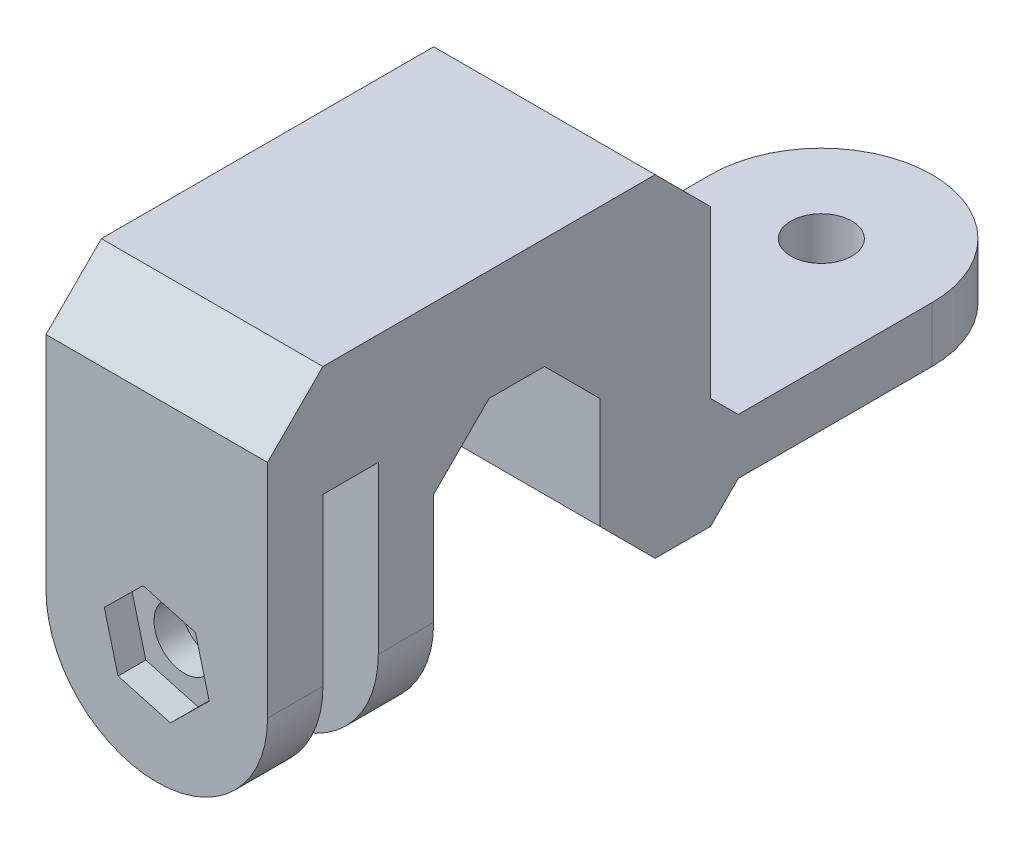
SolidWorks part; units mm, degrees
ref_plane "Front Plane" through (0, 0, 0) normal (0, 0, 1) x (1, 0, 0)
ref_plane "Top Plane" through (0, 0, 0) normal (0, 1, 0) x (1, 0, 0)
ref_plane "Right Plane" through (0, 0, 0) normal (1, 0, 0) x (0, 0, -1)
sketch "Sketch1" plane through (0, 0, 0) normal (0, 0, 1) x (1, 0, 0)
  line L0 (0, -5) -> (0, 5) construction
  line L1 (-10, -5) -> (10, -5)
  line L2 (-10, -5) -> (-10, 5)
  line L3 (-10, 5) -> (10, 5)
  line L4 (10, -5) -> (10, 5)
  dimension "D1" = 10
  dimension "D2" = 20
extrude "Boss-Extrude1" add sketch "Sketch1" along normal blind 10
sketch "Sketch3" plane through (0, 0, 0) normal (0, 0, -1) x (-1, 0, 0)
  line L0 (-10, -5) -> (-10, 5) construction
  line L1 (-10, 2.5) -> (10, 2.5)
  line L2 (-10, 2.5) -> (-10, -2.5)
  line L3 (-10, -2.5) -> (10, -2.5)
  line L4 (10, 2.5) -> (10, -2.5)
  line L5 (10, 5) -> (10, -5) construction
  line L6 (-10, 0) -> (10, 0) construction
  dimension "D1" = 5
extrude "Boss-Extrude2" add sketch "Sketch3" along normal blind 20
fillet "Fillet1" radius 10 2 edges at (-10, 0, -20) (10, 0, -20)
sketch "Sketch4" plane through (-10, 0, 0) normal (-1, 0, 0) x (0, 0, 1)
  line L0 (20, -5) -> (20, 15)
  line L1 (10, -5) -> (20, -5)
  line L2 (10, -5) -> (10, 25)
  line L5 (20, 15) -> (50, 15)
  line L8 (50, 15) -> (50, 25)
  line L9 (50, 25) -> (10, 25)
  line L10 (0, 0) -> (105.2702, 0) construction
  point P8 (0, 0)
  point P12 (0, 0)
  point P13 (0, 0)
  point P14 (0, 0)
  dimension "D1" = 30
  dimension "D2" = 10
  dimension "D3" = 10
  dimension "D4" = 20
extrude "Boss-Extrude3" add sketch "Sketch4" against normal up to surface (20 mm away) up to face at (10, 0, 0)
sketch "Sketch5" plane through (0, 2.5, 0) normal (0, 1, 0) x (1, 0, 0)
  circle A0 centre (0, 10) radius 2.75
  dimension "D1" = 5.5
extrude "Cut-Extrude1" cut sketch "Sketch5" against normal through all both and the other way through all
chamfer "Chamfer1" distance 10 angle 45 2 edges at (0, 5, 0) (0, -5, 0)
sketch "Sketch6" plane through (0, 15, 0) normal (0, -1, 0) x (1, 0, 0)
  line L6 (-10, 42.5) -> (14.1958, 42.5) construction
  line L9 (-10, 40) -> (-10, 35)
  line L10 (10, 45) -> (-10, 45)
  line L11 (10, 45) -> (10, 50)
  line L12 (10, 50) -> (-10, 50)
  line L13 (-10, 45) -> (-10, 50)
  line L14 (10, 35) -> (-10, 35)
  line L15 (10, 40) -> (10, 35)
  line L16 (10, 40) -> (-10, 40)
  line L17 (10, 50) -> (10, 20) construction
  line L18 (-10, 20) -> (-10, 50) construction
  line L19 (10, 50) -> (-10, 50) construction
  point P4 (0, 0)
  point P10 (0, 0)
  point P15 (0, 0)
  point P16 (0, 0)
  point P17 (0, 0)
  point P19 (9.0857, 58.7096)
  point P22 (14.1958, 62.5)
  dimension "D1" = 5
  dimension "D2" = 5
extrude "Boss-Extrude4" add sketch "Sketch6" along normal blind 25
fillet "Fillet2" radius 10 4 edges at (10, -10, 37.5) (-10, -10, 37.5) (-10, -10, 47.5) (10, -10, 47.5)
sketch "Sketch7" plane through (0, 0, 50) normal (0, 0, 1) x (1, 0, 0)
  circle A0 centre (0, 0) radius 2.75
  arc A3 (0, -10) -> (10, 0) centre (0, 0) ccw construction
  point P2 (0, 0)
  dimension "D1" = 5.5
extrude "Cut-Extrude2" cut sketch "Sketch7" against normal up to surface (15 mm away) and the other way through all from surface up to face at (0, 3.1716, 35) starting at face at (0, 7.1716, 50)
chamfer "Chamfer3" distance 5 angle 45 5 edges at (0, -5, 20) (0, 15, 20) (0, 25, 10) (0, 25, 50) (0, 15, 35)
sketch "Sketch8" plane through (0, 0, 50) normal (0, 0, 1) x (1, 0, 0)
  line L1 (4.7319, -1.301) -> (3.4926, 3.4474)
  line L2 (3.4926, 3.4474) -> (-1.2392, 4.7484)
  line L3 (-1.2392, 4.7484) -> (-4.7319, 1.301)
  line L4 (-4.7319, 1.301) -> (-3.4926, -3.4474)
  line L5 (-3.4926, -3.4474) -> (1.2392, -4.7484)
  line L6 (1.2392, -4.7484) -> (4.7319, -1.301)
  circle A0 centre (0, 0) radius 4.25 construction
  circle A1 centre (0, 0) radius 2.75 construction
  point P1 (0, 0)
  dimension "D1" = 8.5
extrude "Cut-Extrude3" cut sketch "Sketch8" against normal blind 2.5
